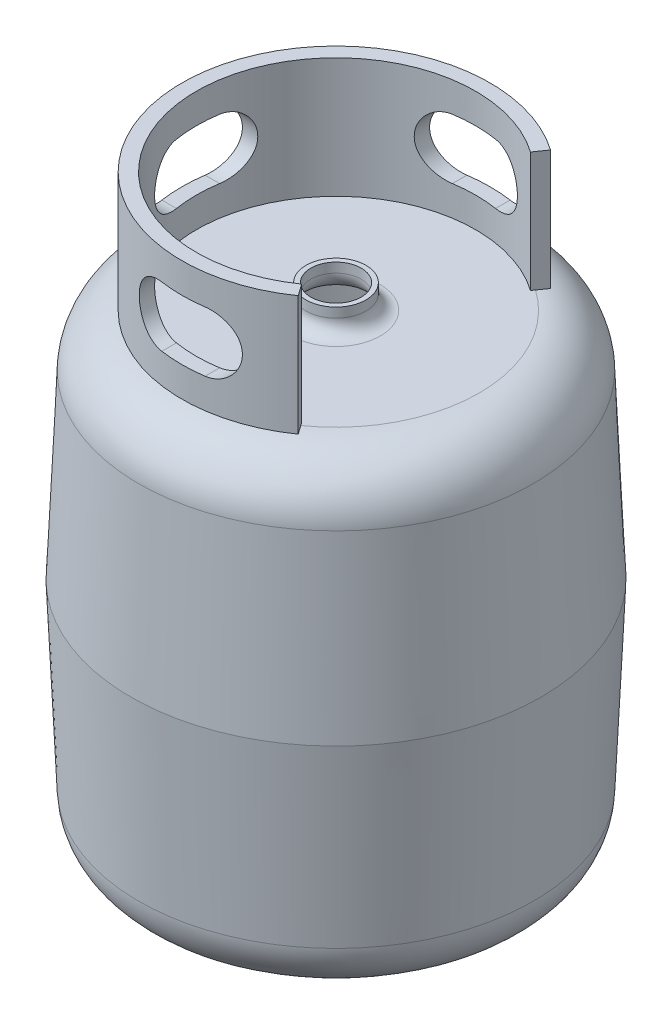
SolidWorks part; units mm, degrees
material "1060 Alloy"
ref_plane "Front Plane" through (0, 0, 0) normal (0, 0, 1) x (1, 0, 0)
ref_plane "Top Plane" through (0, 0, 0) normal (0, 1, 0) x (1, 0, 0)
ref_plane "Right Plane" through (0, 0, 0) normal (1, 0, 0) x (0, 0, -1)
sketch "Sketch6" plane through (0, 0, 0) normal (0, 0, 1) x (1, 0, 0)
  line L0 (0, -243.0441) -> (0, 243.0441) construction
  line L1 (-193.0285, 0) -> (193.0285, 0) construction
  line L2 (0, 213.75) -> (-25, 213.75)
  line L3 (-25, 213.75) -> (-25, 205.75)
  line L4 (-37, 193.75) -> (-119.4219, 193.75)
  line L5 (-164.379, 150.7129) -> (-170.9593, 0)
  line L6 (-170.9593, 0) -> (-164.379, -150.7129)
  line L7 (-119.4219, -193.75) -> (0, -193.75)
  line L8 (0, 213.75) -> (0, -193.75)
  arc A0 (-25, 205.75) -> (-37, 193.75) centre (-37, 205.75) cw
  arc A1 (-164.379, -150.7129) -> (-119.4219, -193.75) centre (-119.4219, -148.75) ccw
  arc A2 (-164.379, 150.7129) -> (-119.4219, 193.75) centre (-119.4219, 148.75) cw
  point P4 (0, 0)
  point P8 (0, 0)
  point P10 (0, 243.0441)
  point P17 (-25, 193.75)
  point P20 (-162.5, -193.75)
  point P23 (-162.5, 193.75)
  dimension "D8" = 12
  dimension "D9" = 45
  dimension "D1" = 25
  dimension "D2" = 20
  dimension "D3" = 193.75
  dimension "D4" = 193.75
  dimension "D5" = 162.5
  dimension "D6" = 162.5
  dimension "D7" = 92.5
revolve "Revolve17" add sketch "Sketch6" angle 360 about L8
shell "Shell3" thickness 4 removed face at (-25, 213.75, 0)
sketch "Sketch8" plane through (0, 193.75, 0) normal (0, 1, 0) x (1, 0, 0)
  line L0 (0, -234.6767) -> (0, 234.6767) construction
  line L1 (376.8822, 0) -> (-376.8822, 0) construction
  line L2 (0, 0) -> (73.6598, 105.197)
  line L3 (0, 0) -> (73.6598, -105.197)
  arc A0 (73.6598, 105.197) -> (73.6598, -105.197) centre (0, 0) ccw
  arc A1 (66.7768, 95.3672) -> (66.7768, -95.3672) centre (0, 0) ccw
  circle A2 centre (0, 0) radius 119.4219 construction
  point P9 (0, 0)
  point P12 (0, 0)
  circle M4 centre (0, 0) radius 119.4219
  dimension "D1" = 3
  dimension "D2" = 12
  dimension "D3" = 55
extrude "Boss-Extrude1" add sketch "Sketch8" along normal blind 100 contours L2 A0 L3 M4 | A1 L2 L3 M4 region at (-116.7258, 193.75, 0) region at (-122.69, 193.75, 0)
sketch "Sketch9" plane through (0, 0, 0) normal (0, 0, 1) x (1, 0, 0)
  line L0 (0, -365.2896) -> (0, 365.2896) construction
  line L1 (-18, 268.75) -> (18, 268.75)
  line L2 (-18, 218.75) -> (18, 218.75)
  line L7 (66.7768, 293.75) -> (-116.4219, 293.75) construction
  arc A0 (18, 218.75) -> (18, 268.75) centre (18, 243.75) ccw
  arc A1 (-18, 218.75) -> (-18, 268.75) centre (-18, 243.75) cw
  point P3 (-43, 243.75)
  point P4 (0, 0)
  point P7 (43, 243.75)
  point P12 (0, 0)
  point P15 (0, 0)
  dimension "D1" = 86
  dimension "D3" = 50
  dimension "D2" = 18
extrude "Cut-Extrude1" cut sketch "Sketch9" against normal blind 378 and the other way blind 388
sketch "Sketch11" plane through (0, 0, 0) normal (1, 0, 0) x (0, 0, -1)
  line L0 (0, -331.4713) -> (0, 331.4713) construction
  line L1 (-18, 243.75) -> (18, 243.75) construction
  line L2 (-18, 268.75) -> (18, 268.75)
  line L3 (-18, 218.75) -> (18, 218.75)
  line L4 (116.4219, 293.75) -> (-116.4219, 293.75) construction
  arc A0 (-18, 268.75) -> (-18, 218.75) centre (-18, 243.75) ccw
  arc A1 (18, 218.75) -> (18, 268.75) centre (18, 243.75) ccw
  point P4 (0, 0)
  point P5 (0, 243.75)
  point P11 (-43, 243.75)
  point P12 (43, 243.75)
  point P17 (-151.6174, 312.665)
  dimension "D1" = 86
  dimension "D2" = 50
  dimension "D3" = 50
extrude "Cut-Extrude2" cut sketch "Sketch11" against normal blind 378
equation "\"A\"= 325"
equation "\"B\"= 387"
